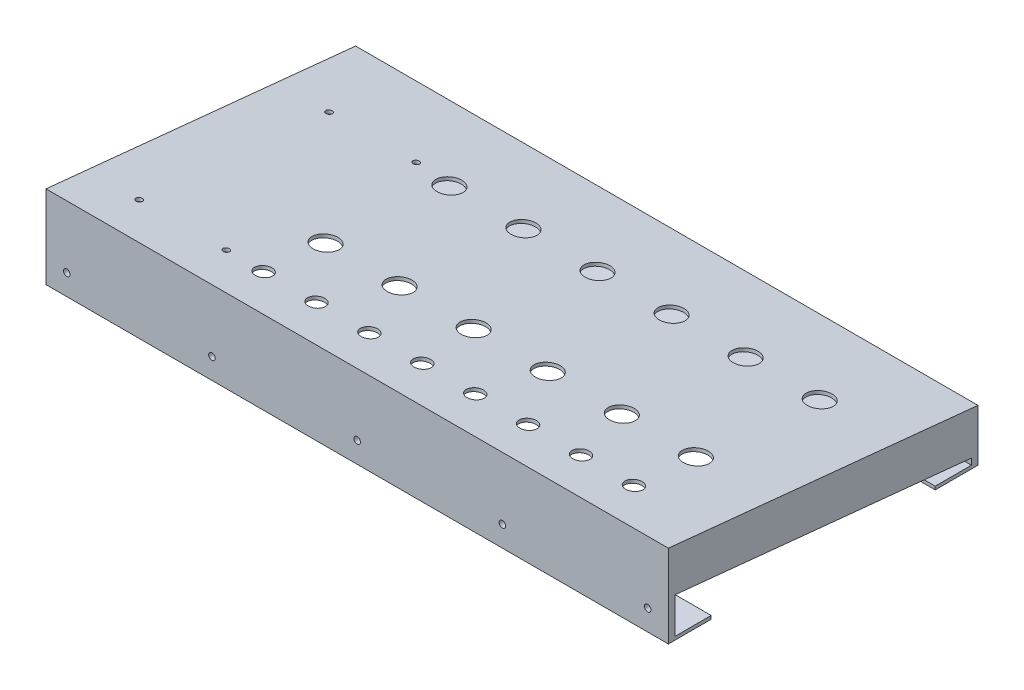
SolidWorks part; units mm, degrees
ref_plane "Plan de face" through (0, 0, 0) normal (0, 0, 1) x (1, 0, 0)
ref_plane "Plan de dessus" through (0, 0, 0) normal (0, 1, 0) x (1, 0, 0)
ref_plane "Plan de droite" through (0, 0, 0) normal (1, 0, 0) x (0, 0, -1)
sketch "Esquisse1" plane through (0, 0, 0) normal (1, 0, 0) x (0, 0, -1)
  line L0 (-26.398, -24.4282) -> (-26.398, 15.5718)
  line L1 (-26.398, 15.5718) -> (122.8501, 0.5718)
  line L2 (122.8501, 0.5718) -> (122.8501, -24.4282)
  line L3 (122.8501, -24.4282) -> (121.2626, -24.4282)
  line L4 (121.2626, -24.4282) -> (121.2626, -0.8641)
  line L5 (121.2626, -0.8641) -> (-24.8105, 13.8168)
  line L6 (-24.8105, 13.8168) -> (-24.8105, -24.4282)
  line L7 (-24.8105, -24.4282) -> (-26.398, -24.4282)
  line L8 (110.6669, 0.2008) -> (110.8256, 1.7803) construction
  point P10 (0, 0)
  dimension "D1" = 1.5875
  dimension "D2" = 40
  dimension "D3" = 25
  dimension "D4" = 150
extrude "Boss.-Extru.1" add sketch "Esquisse1" along normal blind 300
sketch "Esquisse3" plane through (0, 0, 24.8105) normal (0, 0, -1) x (-1, 0, 0)
  line L0 (-300, -24.4282) -> (-300, 13.8168) construction
  line L1 (-300, -5.3782) -> (0, -5.3782)
  line L2 (-300, -5.3782) -> (-300, -24.4282)
  line L3 (-300, -24.4282) -> (0, -24.4282)
  line L4 (0, -5.3782) -> (0, -24.4282)
  line L5 (-300, -24.4282) -> (0, -24.4282) construction
  line L6 (0, -24.4282) -> (0, 13.8168) construction
  dimension "D1" = 19.05
extrude "Boss.-Extru.2" add sketch "Esquisse3" along normal blind 1.5875
sketch "Esquisse4" plane through (0, 0, 23.223) normal (0, 0, -1) x (-1, 0, 0)
  line L0 (-300, -5.3782) -> (-300, -24.4282) construction
  line L1 (-300, -22.8407) -> (0, -22.8407)
  line L2 (-300, -22.8407) -> (-300, -24.4282)
  line L3 (-300, -24.4282) -> (0, -24.4282)
  line L4 (0, -22.8407) -> (0, -24.4282)
  line L5 (-300, -24.4282) -> (0, -24.4282) construction
  line L6 (0, -24.4282) -> (0, -5.3782) construction
  dimension "D1" = 1.5875
extrude "Boss.-Extru.3" add sketch "Esquisse4" along normal blind 17.4625
sketch "Esquisse5" plane through (0, 0, -121.2626) normal (0, 0, 1) x (1, 0, 0)
  line L0 (300, -24.4282) -> (0, -24.4282) construction
  line L1 (0, -5.3782) -> (300, -5.3782)
  line L2 (0, -5.3782) -> (0, -24.4282)
  line L3 (0, -24.4282) -> (300, -24.4282)
  line L4 (300, -5.3782) -> (300, -24.4282)
  line L5 (300, -0.8641) -> (300, -24.4282) construction
  line L6 (0, -0.8641) -> (0, -24.4282) construction
  point P6 (0, 0)
  point P9 (0, 0)
  dimension "D1" = 19.05
extrude "Boss.-Extru.4" add sketch "Esquisse5" along normal blind 1.5875
sketch "Esquisse6" plane through (0, 0, -119.6751) normal (0, 0, 1) x (1, 0, 0)
  line L0 (0, -5.3782) -> (0, -24.4282) construction
  line L1 (0, -22.8407) -> (300, -22.8407)
  line L2 (0, -22.8407) -> (0, -24.4282)
  line L3 (0, -24.4282) -> (300, -24.4282)
  line L4 (300, -22.8407) -> (300, -24.4282)
  point P5 (300, -14.034)
  dimension "D1" = 1.5875
extrude "Boss.-Extru.5" add sketch "Esquisse6" along normal blind 17.4625
sketch "Esquisse7" plane through (300, 0, 0) normal (1, 0, 0) x (0, 0, -1)
  line L0 (-24.8105, 13.8168) -> (-24.8105, 12.2213)
  line L1 (-24.8105, -5.3782) -> (-24.8105, 13.8168) construction
  line L2 (-24.8105, 12.2213) -> (121.2626, -2.4596)
  line L4 (121.2626, -2.4596) -> (121.2626, -0.8641)
  line L5 (121.2626, -0.8641) -> (-24.8105, 13.8168)
  point P5 (121.2626, -3.1211)
  dimension "D1" = 1.5875
extrude "Boss.-Extru.6" add sketch "Esquisse7" against normal blind 19.05
sketch "Esquisse8" plane through (300, 0, 0) normal (1, 0, 0) x (0, 0, -1)
  line L0 (-24.8105, 12.2213) -> (121.2626, -2.4596)
  line L1 (121.2626, -2.4596) -> (121.2626, -5.3782)
  line L2 (121.2626, -5.3782) -> (119.6751, -5.3782)
  line L3 (119.6751, -5.3782) -> (119.6751, -19.8505)
  line L4 (119.6751, -22.8407) -> (119.6751, -5.3782) construction
  line L5 (119.6751, -19.8505) -> (-24.8105, -5.3292)
  line L6 (-24.8105, -5.3782) -> (-24.8105, 12.2213) construction
  line L7 (-24.8105, -5.3292) -> (-24.8105, 12.2213)
  dimension "D1" = 17.4625
extrude "Boss.-Extru.7" add sketch "Esquisse8" against normal blind 1.5875
sketch "Esquisse9" plane through (0, 0, 0) normal (-1, 0, 0) x (0, 0, 1)
  line L0 (-121.2626, -0.8641) -> (24.8105, 13.8168)
  line L1 (24.8105, 13.8168) -> (24.8105, 12.2213)
  line L2 (24.8105, -5.3782) -> (24.8105, 13.8168) construction
  line L3 (24.8105, 12.2213) -> (-121.2626, -2.4596)
  line L4 (-121.2626, -0.8641) -> (-121.2626, -5.3782) construction
  line L5 (-121.2626, -2.4596) -> (-121.2626, -0.8641)
  dimension "D1" = 1.5875
extrude "Boss.-Extru.8" add sketch "Esquisse9" against normal blind 19.05 separate body
sketch "Esquisse11" plane through (0, 0, 0) normal (-1, 0, 0) x (0, 0, 1)
  line L0 (-121.2626, -2.4596) -> (-121.2626, -5.3782)
  line L1 (-121.2626, -5.3782) -> (-119.6751, -5.3782)
  line L2 (-119.6751, -5.3782) -> (-119.6751, -19.8505)
  line L3 (-119.6751, -5.3782) -> (-119.6751, -22.8407) construction
  line L4 (-119.6751, -19.8505) -> (24.8105, -5.3292)
  line L5 (24.8105, -5.3782) -> (24.8105, 13.8168) construction
  line L6 (24.8105, -5.3292) -> (24.8105, 12.2213)
  line L7 (24.8105, 12.2213) -> (-121.2626, -2.4596)
  point P4 (24.8105, 10.8883)
  dimension "D1" = 17.4625
extrude "Boss.-Extru.9" add sketch "Esquisse11" against normal blind 1.5875
sketch "Esquisse12" plane through (0, 0, -122.8501) normal (0, 0, -1) x (-1, 0, 0)
  line L1 (-300, -24.4282) -> (0, -24.4282) construction
  line L2 (-300, -24.4282) -> (-300, 0.5718) construction
  line L3 (0, -24.4282) -> (0, 0.5718) construction
  line L4 (-290, -14.4282) -> (-150, -14.4282) construction
  line L5 (-150, -14.4282) -> (-10, -14.4282) construction
  circle A0 centre (-290, -14.4282) radius 1.5875
  circle A1 centre (-150, -14.4282) radius 1.5875
  circle A2 centre (-10, -14.4282) radius 1.5875
  circle A3 centre (-220, -14.4282) radius 1.5875
  circle A4 centre (-80, -14.4282) radius 1.5875
  point P15 (-150, -24.4282)
  point P17 (0, 0)
  point P18 (-80, -14.4282)
  point P19 (0, 0)
  point P20 (-220, -14.4282)
  dimension "D1" = 3.175
  dimension "D2" = 10
  dimension "D3" = 10
  dimension "D4" = 10
extrude "Enlèv. mat.-Extru.1" cut sketch "Esquisse12" against normal through all
sketch "Esquisse13" plane through (0, 12.7896, -1.2854) normal (0, 0.995, -0.1) x (1, 0, 0)
  line L1 (300, -27.8228) -> (0, -27.8228) construction
  line L2 (0, 122.1772) -> (0, -27.8228) construction
  circle A0 centre (263.5, -7.8228) radius 4
  circle A1 centre (238, -7.8228) radius 4
  circle A2 centre (212.5, -7.8228) radius 4
  circle A3 centre (187, -7.8228) radius 4
  circle A4 centre (161.5, -7.8228) radius 4
  circle A5 centre (136, -7.8228) radius 4
  circle A6 centre (110.5, -7.8228) radius 4
  circle A7 centre (85, -7.8228) radius 4
  circle A8 centre (263.5, 22.1772) radius 6
  circle A9 centre (227.8, 22.1772) radius 6
  circle A10 centre (192.1, 22.1772) radius 6
  circle A11 centre (156.4, 22.1772) radius 6
  circle A12 centre (120.7, 22.1772) radius 6
  circle A13 centre (85, 22.1772) radius 6
  circle A14 centre (227.8, 82.1772) radius 6
  circle A15 centre (192.1, 82.1772) radius 6
  circle A16 centre (156.4, 82.1772) radius 6
  circle A17 centre (120.7, 82.1772) radius 6
  circle A18 centre (85, 82.1772) radius 6
  circle A19 centre (263.5, 82.1772) radius 6
  circle A20 centre (67, -7.8228) radius 1.5
  circle A21 centre (25, -7.8228) radius 1.5
  circle A22 centre (67, 84.1772) radius 1.5
  circle A23 centre (25, 84.1772) radius 1.5
  dimension "D1" = 8
  dimension "D5" = 12
  dimension "D6" = 6
  dimension "D10" = 3
  dimension "D3" = 85
  dimension "D4" = 20
  dimension "D8" = 85
  dimension "D9" = 50
  dimension "D11" = 42
  dimension "D12" = 92
  dimension "D13" = 25
  dimension "D14" = 20
  dimension "D2" = 8
  dimension "D7" = 2
extrude "Enlèv. mat.-Extru.2" cut sketch "Esquisse13" against normal up to next
